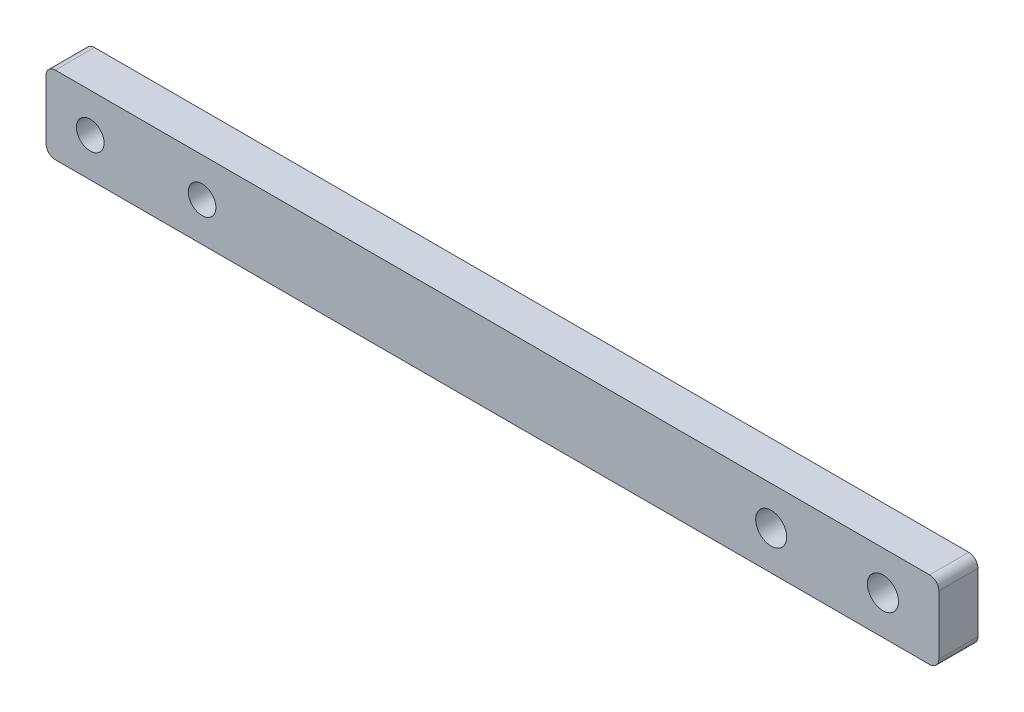
SolidWorks part; units mm, degrees
ref_plane "Front" through (0, 0, 0) normal (0, 0, 1) x (1, 0, 0)
ref_plane "Top" through (0, 0, 0) normal (0, 1, 0) x (1, 0, 0)
ref_plane "Right" through (0, 0, 0) normal (1, 0, 0) x (0, 0, -1)
sketch "Sketch1" plane through (0, 0, 0) normal (0, 0, 1) x (1, 0, 0)
  line L0 (59.309, 3.175) -> (68.453, 3.175) construction
  line L1 (0, 6.35) -> (73.025, 6.35)
  line L2 (0, 6.35) -> (0, 0)
  line L3 (0, 0) -> (73.025, 0)
  line L4 (73.025, 6.35) -> (73.025, 0)
  line L5 (63.881, 6.35) -> (63.881, 0) construction
  line L6 (3.6195, 3.175) -> (12.7635, 3.175) construction
  line L8 (8.1915, 6.35) -> (8.1915, 0) construction
  circle A0 centre (59.309, 3.175) radius 1.27
  circle A1 centre (68.453, 3.175) radius 1.27
  circle A2 centre (3.6195, 3.175) radius 1.1303
  circle A3 centre (12.7635, 3.175) radius 1.1303
  point P9 (63.881, 3.175)
  point P20 (8.1915, 3.175)
  dimension "D5" = 2.54
  dimension "D6" = 2.2606
  dimension "D1" = 73.025
  dimension "D2" = 6.35
  dimension "D3" = 9.144
  dimension "D4" = 9.144
  dimension "D7" = 8.1915
extrude "Boss-Extrude1" add sketch "Sketch1" along normal blind 3.2004
fillet "Fillet1" radius 0.762 4 edges at (0, 0, 1.6002) (73.025, 0, 1.6002) (73.025, 6.35, 1.6002) (0, 6.35, 1.6002)
